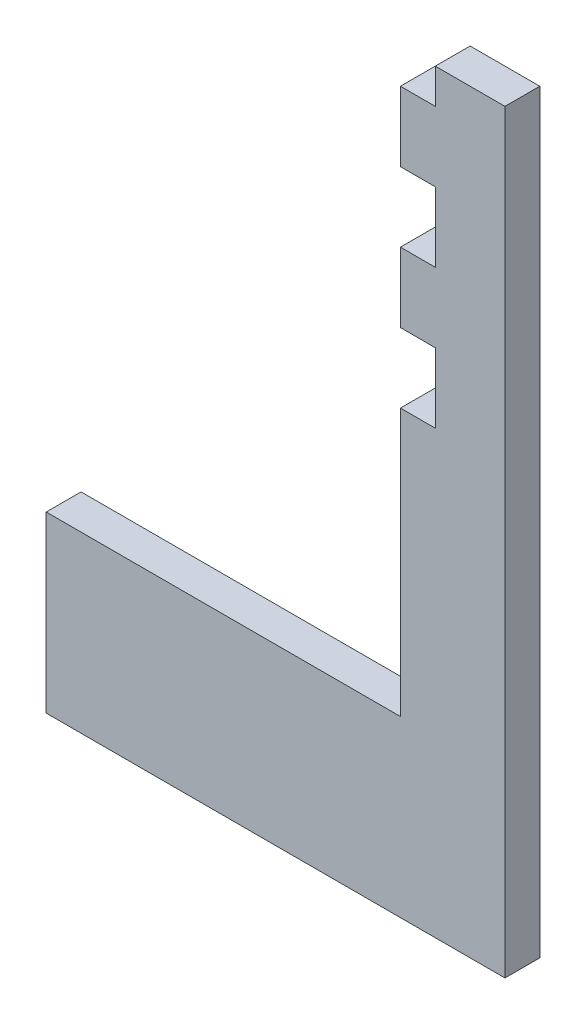
SolidWorks part; units mm, degrees
ref_plane "Front Plane" through (0, 0, 0) normal (0, 0, 1) x (1, 0, 0)
ref_plane "Top Plane" through (0, 0, 0) normal (0, 1, 0) x (1, 0, 0)
ref_plane "Right Plane" through (0, 0, 0) normal (1, 0, 0) x (0, 0, -1)
sketch "Sketch1" plane through (0, 0, 0) normal (0, 0, 1) x (1, 0, 0)
  line L3 (79, 0) -> (0, 0)
  line L4 (0, 0) -> (0, -30)
  line L5 (0, -30) -> (79, -30)
  line L6 (79, -30) -> (79, 0)
  line L9 (0, 0) -> (20, 0)
  line L26 (0, 0) -> (0, -30)
  line L28 (79, 0) -> (61, 0)
  line L29 (79, 0) -> (79, 100)
  line L30 (79, 100) -> (61, 100)
  line L31 (61, 0) -> (61, 100)
  dimension "D1" = 18
  dimension "D2" = 100
  dimension "D3" = 79
  dimension "D4" = 30
extrude "Boss-Extrude4" add sketch "Sketch1" along normal blind 6 contours L31 L3 region at (70, 50, 0)
extrude "Boss-Extrude5" add sketch "Sketch1<8>" along normal blind 6 contours L5 L6 L3 L4 region at (39.5, -15, 0)
sketch "Sketch1<8>" plane through (0, 0, 0) normal (0, 0, 1) x (1, 0, 0) same geometry as "Sketch1"
sketch "Sketch3" plane through (0, 0, 6) normal (0, 0, 1) x (1, 0, 0)
  line L1 (0, -10) -> (79, -10)
  line L2 (0, -10) -> (0, -20)
  line L3 (0, -20) -> (79, -20)
  line L4 (79, -10) -> (79, -20)
  line L5 (79, -30) -> (79, 100) construction
  dimension "D1" = 10
  dimension "D2" = 10
sketch "Sketch4" plane through (0, 0, 0) normal (0, 0, -1) x (-1, 0, 0)
  line L1 (-61, 106) -> (-67, 106)
  line L2 (-61, 106) -> (-61, 94)
  line L3 (-61, 94) -> (-67, 94)
  line L4 (-67, 106) -> (-67, 94)
  line L6 (-79, 100) -> (-61, 100) construction
  line L7 (-61, 0) -> (-61, 100) construction
  line L8 (-61, 82) -> (-61, 70)
  line L9 (-61, 82) -> (-67, 82)
  line L10 (-67, 82) -> (-67, 70)
  line L11 (-61, 70) -> (-67, 70)
  line L12 (-61, 58) -> (-61, 46)
  line L13 (-61, 58) -> (-67, 58)
  line L14 (-67, 58) -> (-67, 46)
  line L15 (-61, 46) -> (-67, 46)
  dimension "D1" = 6
  dimension "D2" = 12
  dimension "D3" = 6
  dimension "D4" = 3
extrude "Cut-Extrude1" cut sketch "Sketch4" against normal up to next
